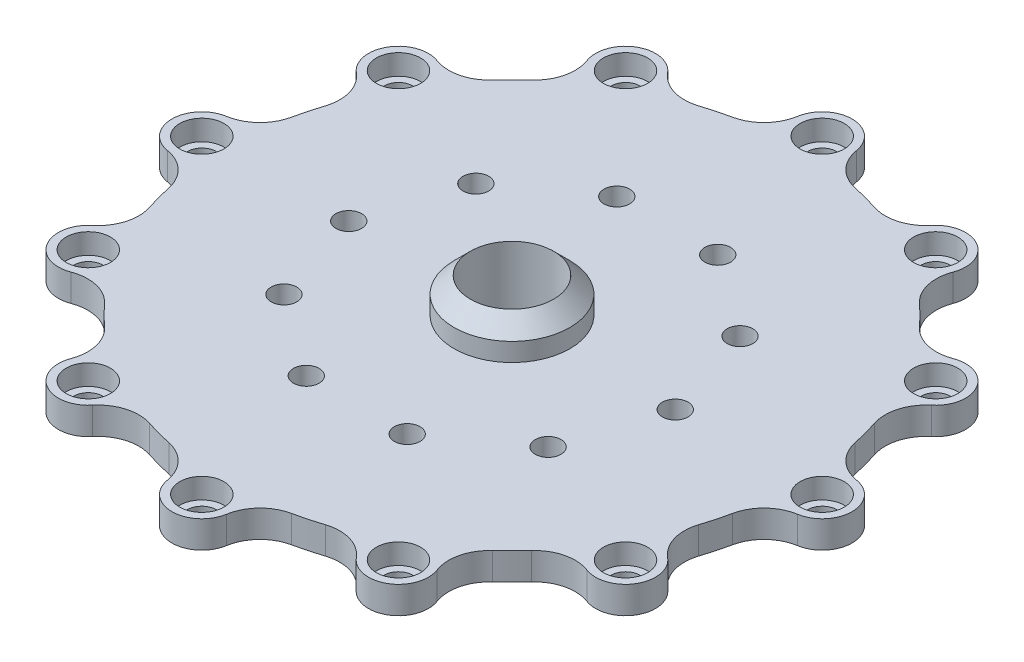
SolidWorks part; units mm, degrees
material "Nickel"
ref_plane "Front Plane" through (0, 0, 0) normal (0, 0, 1) x (1, 0, 0)
ref_plane "Top Plane" through (0, 0, 0) normal (0, 1, 0) x (1, 0, 0)
ref_plane "Right Plane" through (0, 0, 0) normal (1, 0, 0) x (0, 0, -1)
sketch "Sketch1" plane through (0, 0, 0) normal (0, 0, 1) x (1, 0, 0)
  line L0 (79.375, 10.6858) -> (79.375, 17.0358)
  line L1 (0, 0) -> (0, 52.0897) construction
  line L3 (79.375, 10.6858) -> (19.2253, 10.6858)
  line L4 (79.375, 17.0358) -> (13.5204, 17.0358)
  line L5 (9.7104, 25.1308) -> (9.7104, 0)
  line L6 (14.1453, -4.4348) -> (19.2253, -4.4348)
  line L10 (19.2253, -4.4348) -> (19.2253, 10.6858)
  line L11 (9.7104, 25.1308) -> (13.5204, 25.1308)
  line L12 (13.5204, 25.1308) -> (13.5204, 17.0358)
  line L15 (14.1453, -4.4348) -> (9.7104, 0)
  dimension "D1" = 79.375
  dimension "D2" = 9.7104
  dimension "D3" = 15.1206
  dimension "D4" = 6.35
  dimension "D5" = 19.2253
  dimension "D8" = 135
  dimension "D9" = 5.08
  dimension "D10" = 3.81
  dimension "D11" = 8.095
revolve "Revolve1" add sketch "Sketch1" angle 360 about L1
chamfer "Chamfer1" distance 3.81 angle 45 1 edges at (13.5204, 25.1308, 0)
hole_wizard "Hole2" positions "Sketch5" profile "Sketch6" legacy end condition up to next
sketch "Sketch5" plane through (0, 17.0358, 0) normal (0, 1, 0) x (1, 0, 0)
  line L0 (0, 0) -> (38.1, 0) construction
  point P0 (38.1, 0)
  dimension "D1" = 38.1
sketch "Sketch6" plane through (38.1, 17.0358, 0) normal (1, 0, 0) x (0, 0, 1)
  line L0 (0, 0) -> (0, 6.351)
  line L1 (0, 6.351) -> (3, 6.351)
  line L2 (3, 6.351) -> (3, 0)
  line L3 (3, 0) -> (0, 0)
  line L4 (0, 110) -> (0, -10) construction
  dimension "Diameter" = 6
  dimension "Depth" = 6.351
pattern_circular "CirPattern2" count 10 over 360 about axis through (0, 0, 0) along (0, 1, 0) of "Hole2"
hole_wizard "CBORE for 1/4 Socket Shoulder Screw1" positions "Sketch11" profile "Sketch13" counterbore size "1/4" standard "ANSI Inch" end condition through all
sketch "Sketch11" plane through (0, 17.0358, 0) normal (0, 1, 0) x (1, 0, 0)
  line L0 (0, 0) -> (72.39, 0)
  point P0 (72.39, 0)
  dimension "D1" = 72.39
sketch "Sketch13" plane through (72.39, 17.0358, 0) normal (1, 0, 0) x (0, 0, 1)
  line L0 (0, 0) -> (0, 21.4706)
  line L1 (0, 21.4706) -> (3.3782, 21.4706)
  line L3 (3.3782, 21.4706) -> (3.3782, 4.7752)
  line L4 (3.3782, 4.7752) -> (5.1587, 4.7752)
  line L5 (5.1587, 4.7752) -> (5.1587, 0)
  line L7 (5.1587, 0) -> (0, 0)
  line L11 (0, -6.35) -> (0, 107.95) construction
  dimension "Thru Hole Dia." = 6.7564
  dimension "Thru Hole Depth" = 21.4706
  dimension "C'Bore Dia." = 10.3175
  dimension "C'Bore Depth" = 4.7752
pattern_circular "CirPattern4" count 12 over 360 about axis through (0, 0, 0) along (0, 1, 0) of "CBORE for 1/4 Socket Shoulder Screw1"
sketch "Sketch17" plane through (0, 17.0358, 0) normal (0, 1, 0) x (1, 0, 0)
  arc A0 (79.375, 0) -> (73.5318, 6.891) centre (72.39, 0) ccw
  arc A1 (67.1259, 30.7981) -> (68.7408, 39.6875) centre (62.6916, 36.195) ccw
  arc A2 (65.7802, 14.2688) -> (64.1017, 20.533) centre (0, 0) ccw
  circle A3 centre (0, 0) radius 79.375 construction
  arc A4 (79.375, 0) -> (68.7408, 39.6875) centre (0, 0) ccw
  circle A5 centre (62.6916, 36.195) radius 5.1587 construction
  arc A6 (65.7802, 14.2688) -> (73.5318, 6.891) centre (75.0888, 16.2879) ccw
  circle A7 centre (72.39, 0) radius 5.1587 construction
  arc A8 (67.1259, 30.7981) -> (64.1017, 20.533) centre (73.1727, 23.4386) ccw
  dimension "D1" = 134.62
  dimension "D2" = 19.05
extrude "Cut-Extrude3" cut sketch "Sketch17" against normal up to next
pattern_circular "CirPattern5" count 12 over 360 about axis through (0, 0, 0) along (0, 1, 0) of "Cut-Extrude3"
